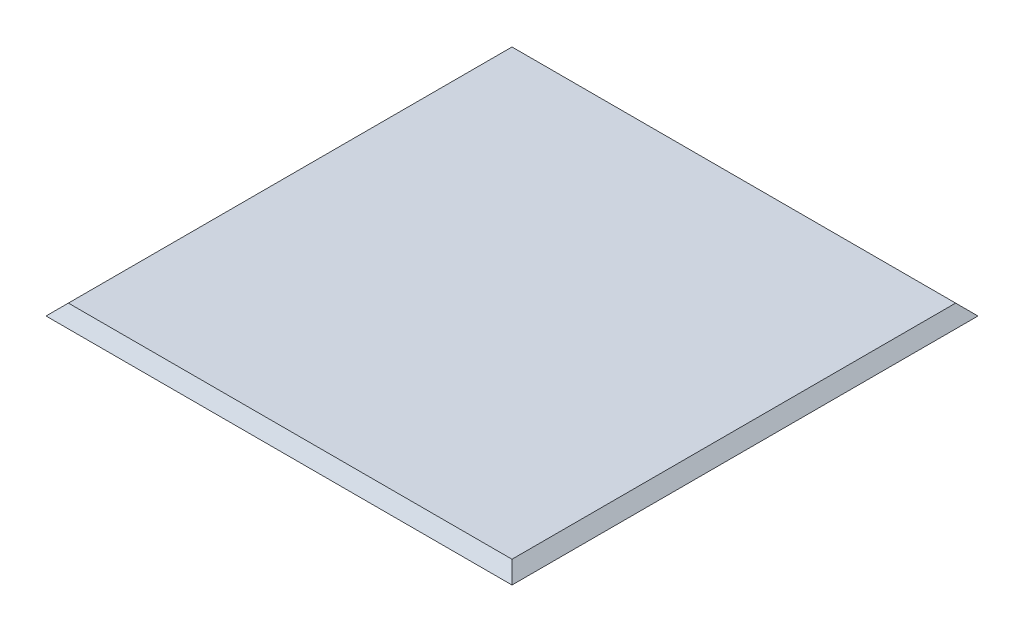
SolidWorks part; units mm, degrees
other "Markup1"
sketch "Sketch4" plane through (0, 750, 0) normal (-0.3936, 0.2648, -0.8803) x (-0.8349, 0.2978, 0.4628)
ref_plane "Front Plane" through (0, 0, 0) normal (0, 0, 1) x (1, 0, 0)
ref_plane "Top Plane" through (0, 0, 0) normal (0, 1, 0) x (1, 0, 0)
ref_plane "Right Plane" through (0, 0, 0) normal (1, 0, 0) x (0, 0, -1)
sketch "Sketch5" plane through (0, 0, 0) normal (0, 1, 0) x (1, 0, 0)
  line L1 (0, 0) -> (500, 0)
  line L2 (0, 0) -> (0, 500)
  line L3 (0, 500) -> (500, 500)
  line L4 (500, 0) -> (500, 500)
  dimension "D1" = 500
  dimension "D2" = 500
extrude "Boss-Extrude1" add sketch "Sketch5" along normal blind 12
chamfer "Chamfer1" distance 12 4 edges at (500, 12, -250) (250, 12, -500) (0, 12, -250) (250, 12, 0)
